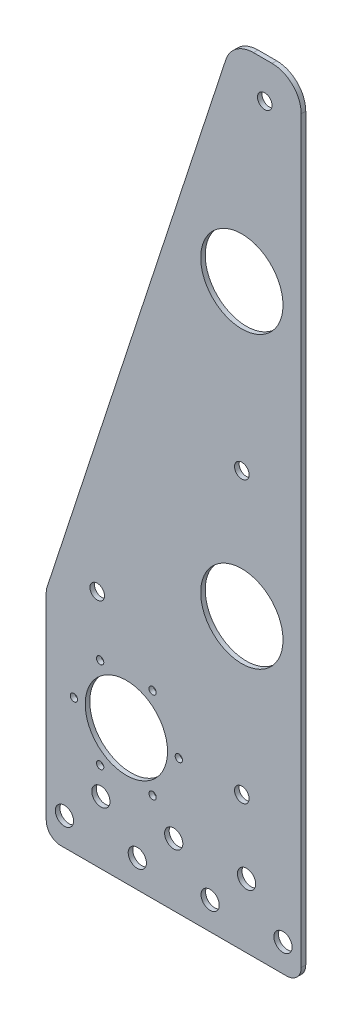
SolidWorks part; units mm, degrees
material "6061 Alloy"
ref_plane "Front Plane" through (0, 0, 0) normal (0, 0, 1) x (1, 0, 0)
ref_plane "Top Plane" through (0, 0, 0) normal (0, 1, 0) x (1, 0, 0)
ref_plane "Right Plane" through (0, 0, 0) normal (1, 0, 0) x (0, 0, -1)
sketch "Sketch1" plane through (0, 0, 0) normal (0, 0, 1) x (1, 0, 0)
  line L2 (88.9, 212.09) -> (88.9, 5.08)
  line L3 (83.82, 0) -> (5.08, 0)
  line L4 (78.74, 222.25) -> (55.6253, 222.25)
  line L5 (45.9692, 215.25) -> (0.252, 75.55)
  line L6 (0, 73.97) -> (0, 5.08)
  line L7 (6.35, 9.652) -> (31.75, 9.652) construction
  line L8 (27.94, 46.99) -> (27.94, 82.7405) construction
  line L9 (27.94, 46.99) -> (60.7143, 46.99) construction
  circle A0 centre (68.199, 201.93) radius 14.351
  circle A1 centre (68.199, 100.838) radius 14.351
  circle A2 centre (68.199, 144.78) radius 2.54
  circle A3 centre (68.199, 46.99) radius 2.54
  arc A4 (78.74, 222.25) -> (88.9, 212.09) centre (78.74, 212.09) cw
  arc A5 (0, 5.08) -> (5.08, 0) centre (5.08, 5.08) ccw
  arc A6 (88.9, 5.08) -> (83.82, 0) centre (83.82, 5.08) cw
  arc A7 (55.6253, 222.25) -> (45.9692, 215.25) centre (55.6253, 212.09) ccw
  arc A8 (0.252, 75.55) -> (0, 73.97) centre (5.08, 73.97) ccw
  circle A9 centre (27.94, 46.99) radius 14.351
  circle A17 centre (68.199, 201.93) radius 50.8 construction
  circle A18 centre (68.199, 100.838) radius 38.1 construction
  circle A19 centre (6.35, 9.652) radius 3.175
  circle A21 centre (31.75, 9.652) radius 3.175
  circle A22 centre (57.15, 9.652) radius 3.175
  circle A23 centre (82.55, 9.652) radius 3.175
  circle A29 centre (69.85, 22.352) radius 3.175
  circle A30 centre (44.45, 21.844) radius 3.175
  circle A31 centre (19.05, 21.844) radius 3.175
  circle A32 centre (46.228, 46.99) radius 1.27
  circle A38 centre (37.084, 31.1521) radius 1.27
  circle A39 centre (18.796, 31.1521) radius 1.27
  circle A40 centre (9.652, 46.99) radius 1.27
  circle A41 centre (18.796, 62.8279) radius 1.27
  circle A42 centre (37.084, 62.8279) radius 1.27
  point P17 (88.9, 222.25)
  point P20 (0, 0)
  point P23 (88.9, 0)
  point P25 (48.26, 222.25)
  point P26 (48.26, 222.25)
  point P43 (27.94, 46.99)
  point P69 (27.94, 46.99)
  dimension "D1" = 28.702
  dimension "D2" = 28.702
  dimension "D4" = 88.9
  dimension "D7" = 5.08
  dimension "D9" = 5.08
  dimension "D11" = 10.16
  dimension "D12" = 5.08
  dimension "D13" = 10.16
  dimension "D14" = 5.08
  dimension "D16" = 28.702
  dimension "D17" = 18.288
  dimension "D23" = 139.7
  dimension "D24" = 101.6
  dimension "D25" = 76.2
  dimension "D26" = 6.35
  dimension "D29" = 21.844
  dimension "D31" = 6.35
  dimension "D32" = 4
  dimension "D34" = 19.05
  dimension "D39" = 21.844
  dimension "D30" = 6.35
  dimension "D35" = 6.35
  dimension "D37" = 6.35
  dimension "D38" = 25.4
  dimension "D18" = 2.54
  dimension "D3" = 101.092
  dimension ".75" = 20.701
  dimension "D5" = 222.25
  dimension "D6" = 20.32
  dimension "D8" = 57.15
  dimension "D10" = 97.79
  dimension "D15" = 40.64
  dimension "D20" = 27.94
  dimension "D21" = 9.144
  dimension "D22" = 15.8379
  dimension "D27" = 9.652
  dimension "D28" = 25.4
  dimension "D33" = 12.7
  dimension "D36" = 25.4
  dimension "D19" = 6
extrude "Boss-Extrude1" add sketch "Sketch1" along normal blind 1.5875
sketch "Sketch2" plane through (0, 0, 1.5875) normal (0, 0, 1) x (1, 0, 0)
  line L0 (45.9692, 215.25) -> (62.5937, 266.05)
  line L1 (45.9692, 215.25) -> (0.252, 75.55) construction
  line L2 (72.2498, 273.05) -> (78.74, 273.05)
  line L3 (88.9, 262.89) -> (88.9, 212.09)
  line L4 (78.74, 222.25) -> (55.6253, 222.25) construction
  line L5 (45.9692, 215.25) -> (55.6253, 222.25)
  line L6 (55.6253, 222.25) -> (78.74, 222.25)
  line L7 (78.74, 222.25) -> (88.9, 212.09)
  line L8 (76.2, 156.304) -> (76.2, 48.354) construction
  line L9 (88.9, 5.08) -> (88.9, 212.09) construction
  arc A0 (78.74, 273.05) -> (88.9, 262.89) centre (78.74, 262.89) cw
  arc A1 (62.5937, 266.05) -> (72.2498, 273.05) centre (72.2498, 262.89) cw
  circle A2 centre (76.2, 260.35) radius 2.54
  point P19 (68.199, 144.78)
  dimension "D2" = 10.16
  dimension "D3" = 5.08
  dimension "D1" = 50.8
  dimension "D4" = 12.7
  dimension "D5" = 12.7
extrude "Boss-Extrude2" add sketch "Sketch2" against normal blind 1.5875
sketch "Sketch3" plane through (0, 0, 1.5875) normal (0, 0, 1) x (1, 0, 0)
  line L0 (68.199, 83.058) -> (-39.9215, 83.058) construction
  line L1 (17.78, 46.99) -> (17.78, -14.087) construction
  circle A1 centre (17.78, 83.058) radius 2.54
  point P0 (68.199, 100.838)
  point P2 (27.94, 46.99)
  dimension "D1" = 5.08
  dimension "D2" = 10.16
  dimension "D3" = 17.78
extrude "Cut-Extrude1" cut sketch "Sketch3" against normal through all contours A1
